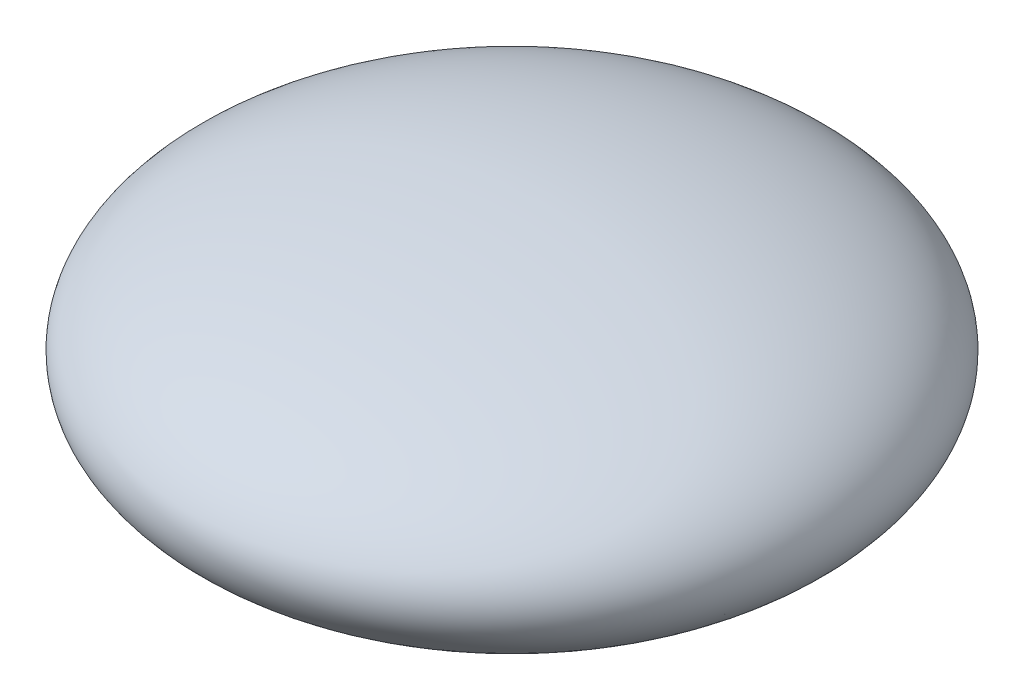
SolidWorks part; units mm, degrees
material "Nylon 101"
ref_plane "Front Plane" through (0, 0, 0) normal (0, 0, 1) x (1, 0, 0)
ref_plane "Top Plane" through (0, 0, 0) normal (0, 1, 0) x (1, 0, 0)
ref_plane "Right Plane" through (0, 0, 0) normal (1, 0, 0) x (0, 0, -1)
sketch "Sketch1" plane through (0, 0, 0) normal (0, 0, 1) x (1, 0, 0)
  line L3 (0, 509.27) -> (0, 508)
  line L5 (0, -508) -> (0, -509.27)
  line L6 (0, 509.27) -> (0, -509.27) construction
  line L8 (0, 0) -> (-1372.87, 0) construction
  ellipse E0 centre (0, 0) end of major axis (-1371.6, 0) minor radius 508 (0, 508) -> (0, -508) ccw
  ellipse E1 centre (0, 0) end of major axis (-1372.87, 0) minor radius 509.27 (0, 509.27) -> (0, -509.27) ccw
revolve "Revolve2" add sketch "Sketch1" angle 360 about L3
sketch "Sketch2" plane through (0, 0, 0) normal (0, 1, 0) x (1, 0, 0)
  line L1 (-970.7657, 970.7657) -> (970.7657, 970.7657)
  line L2 (-970.7657, 970.7657) -> (-970.7657, -970.7657)
  line L3 (-970.7657, -970.7657) -> (970.7657, -970.7657)
  line L4 (970.7657, 970.7657) -> (970.7657, -970.7657)
  line L5 (-970.7657, 970.7657) -> (970.7657, -970.7657) construction
  line L6 (-970.7657, -970.7657) -> (970.7657, 970.7657) construction
  point P0 (0, 0)
  dimension "D1" = 1941.5314
ref_point "Point1"
ref_axis "Axis1" through (-970.7657, 0, 970.7657) along (0.7071, 0, -0.7071)
ref_point "Point2"
ref_axis "Axis2" through (-970.7657, 0, -970.7657) along (0.7071, 0, 0.7071)
ref_point "Point3"
ref_point "Point4"
ref_point "Point5"
